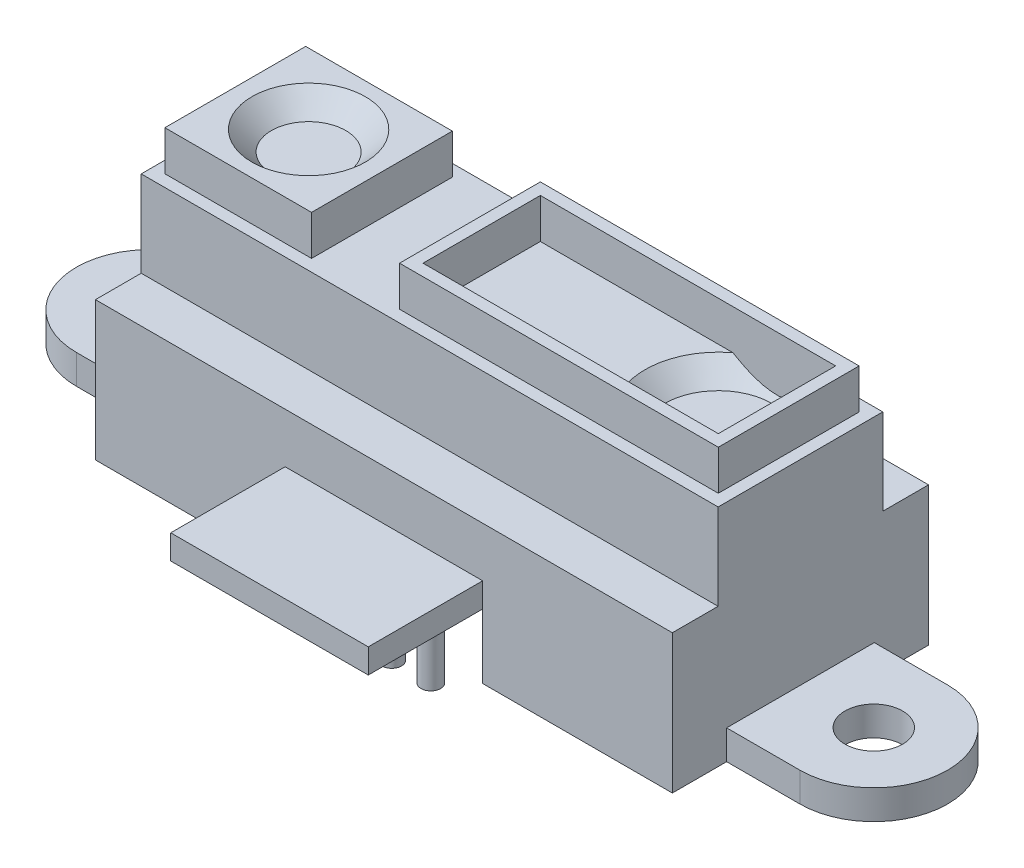
SolidWorks part; units mm, degrees
ref_plane "Front Plane" through (0, 0, 0) normal (0, 0, 1) x (1, 0, 0)
ref_plane "Top Plane" through (0, 0, 0) normal (0, 1, 0) x (1, 0, 0)
ref_plane "Right Plane" through (0, 0, 0) normal (1, 0, 0) x (0, 0, -1)
sketch "Sketch1" plane through (0, 0, 0) normal (0, 1, 0) x (1, 0, 0)
  line L0 (-24.667, 0) -> (35.816, 0) construction
  line L1 (-14.75, 6.55) -> (14.75, 6.55)
  line L2 (-14.75, 6.55) -> (-14.75, -6.55)
  line L3 (-14.75, -6.55) -> (14.75, -6.55)
  line L4 (14.75, 6.55) -> (14.75, -6.55)
  line L5 (-14.75, 6.55) -> (14.75, -6.55) construction
  line L6 (-14.75, -6.55) -> (14.75, 6.55) construction
  line L7 (-22.275, 0) -> (-22.275, -6.55) construction
  line L8 (-22.275, -6.55) -> (-14.75, -6.55) construction
  line L9 (0, 6.55) -> (0, -6.55) construction
  line L10 (-18.5, 3.775) -> (-14.75, 3.775)
  line L11 (-18.5, -3.775) -> (-14.75, -3.775)
  line L12 (18.5, 3.775) -> (14.75, 3.775)
  line L13 (18.5, -3.775) -> (14.75, -3.775)
  circle A0 centre (-18.5, 0) radius 3.775
  circle A1 centre (-18.5, 0) radius 1.4736
  circle A2 centre (18.5, 0) radius 1.4736
  circle A3 centre (18.5, 0) radius 3.775
  point P0 (0, 0)
  dimension "D4" = 7.55
  dimension "D5" = 2.9472
  dimension "D1" = 13.1
  dimension "D2" = 29.5
  dimension "D3" = 44.55
extrude "Boss-Extrude1" add sketch "Sketch1" along normal blind 1.5 contours A0 L2 A1 | A0 L11 L2 | L2 A0 | A0 L2 L10 | L4 A3 L1 L2 A0 L3 | L13 A3 L4 | A3 L4 A2 | L4 A3 L12 | A3 L4 region at (0, 0, 0) region at (-15.5926, 0, -2.9582) region at (15.5926, 0, -2.9582) region at (-14.74, 0, 0) region at (-14.8566, 0, 0) region at (16.0596, 0, -2.7389) region at (14.74, 0, 0) region at (-15.5926, 0, 2.9582) region at (15.5926, 0, 2.9582)
sketch "Sketch2" plane through (0, 1.5, 0) normal (0, 1, 0) x (1, 0, 0)
  line L1 (14.75, 6.55) -> (-14.75, 6.55)
  line L2 (14.75, 6.55) -> (14.75, -6.55)
  line L3 (14.75, -6.55) -> (-14.75, -6.55)
  line L4 (-14.75, 6.55) -> (-14.75, -6.55)
  line L5 (14.75, 6.55) -> (-14.75, -6.55) construction
  line L6 (14.75, -6.55) -> (-14.75, 6.55) construction
  point P0 (0, 0)
extrude "Boss-Extrude2" add sketch "Sketch2" along normal offset from surface (5.6 mm away) 7.1 up to face at (0, 0, 0)
sketch "Sketch3" plane through (0, 7.1, 0) normal (0, 1, 0) x (1, 0, 0)
  line L0 (14.75, -6.55) -> (14.75, 6.55) construction
  line L1 (-14.75, 4.21) -> (14.75, 4.21)
  line L2 (-14.75, 4.21) -> (-14.75, -4.21)
  line L3 (-14.75, -4.21) -> (14.75, -4.21)
  line L4 (14.75, 4.21) -> (14.75, -4.21)
  line L5 (-14.75, 4.21) -> (14.75, -4.21) construction
  line L6 (-14.75, -4.21) -> (14.75, 4.21) construction
  point P0 (0, 0)
  dimension "D1" = 8.42
extrude "Boss-Extrude3" add sketch "Sketch3" along normal offset from surface (4.4 mm away) 11.5 up to face at (0, 0, 0)
sketch "Sketch4" plane through (0, 11.5, 0) normal (0, 1, 0) x (1, 0, 0)
  line L0 (-14.75, 0) -> (14.75, 0) construction
  line L1 (-14.75, 4.21) -> (-14.75, -4.21) construction
  line L2 (14.75, -3.775) -> (14.75, 3.775) construction
  line L3 (-14.15, 3.6) -> (-14.75, 3.6) construction
  line L4 (-14.15, 3.6) -> (-6.65, 3.6)
  line L5 (-14.15, 3.6) -> (-14.15, -3.6)
  line L6 (-14.15, -3.6) -> (-6.65, -3.6)
  line L7 (-6.65, 3.6) -> (-6.65, -3.6)
  line L8 (-14.15, 3.6) -> (-6.65, -3.6) construction
  line L9 (-14.15, -3.6) -> (-6.65, 3.6) construction
  line L10 (-2.15, 3.6) -> (14.15, 3.6)
  line L11 (-2.15, 3.6) -> (-2.15, -3.6)
  line L12 (-2.15, -3.6) -> (14.15, -3.6)
  line L13 (14.15, 3.6) -> (14.15, -3.6)
  line L14 (-2.15, 3.6) -> (14.15, -3.6) construction
  line L15 (-2.15, -3.6) -> (14.15, 3.6) construction
  line L16 (14.15, 3.6) -> (14.75, 3.6) construction
  line L17 (13.55, 3) -> (14.15, 3) construction
  line L18 (-1.55, -3) -> (13.55, -3)
  line L19 (-1.55, -3) -> (-1.55, 3)
  line L20 (-1.55, 3) -> (13.55, 3)
  line L21 (13.55, -3) -> (13.55, 3)
  line L22 (-1.55, -3) -> (13.55, 3) construction
  line L23 (-1.55, 3) -> (13.55, -3) construction
  line L24 (13.55, 3) -> (13.55, 3.6) construction
  point P6 (-10.4, 0)
  point P11 (6, 0)
  point P16 (6, 0)
  dimension "D1" = 7.5
  dimension "D2" = 7.2
  dimension "D3" = 0.6
  dimension "D4" = 16.3
  dimension "D5" = 0.6
extrude "Boss-Extrude4" add sketch "Sketch4" along normal offset from surface (2.04 mm away) 13.54 contours L7 L4 L5 L6 | L13 L10 L11 L12 L21 L18 L19 L20 region at (-10.4, 11.5, 0) region at (6, 11.5, -3.4218) up to face at (0, 0, 0)
sketch "Sketch5" plane through (0, 13.54, 0) normal (0, 1, 0) x (1, 0, 0)
  line L0 (-14.15, 3.6) -> (-6.65, -3.6) construction
  circle A0 centre (-10.4, 0) radius 2.9
  dimension "D1" = 5.8
extrude "Cut-Extrude1" cut sketch "Sketch5" against normal blind 1
sketch "Sketch6" plane through (0, 11.5, 0) normal (0, 1, 0) x (1, 0, 0)
  line L0 (-1.55, 0) -> (13.55, 0) construction
  line L1 (-1.55, -3) -> (-1.55, 3) construction
  line L2 (13.55, -3) -> (13.55, 3) construction
  line L3 (13.55, -3) -> (13.55, 3) construction
  line L8 (13.55, -3) -> (13.55, 3)
  line L9 (13.55, 3) -> (-1.55, 3)
  line L10 (-1.55, 3) -> (-1.55, -3)
  line L11 (-1.55, -3) -> (13.55, -3)
  line L12 (13.55, -3) -> (13.55, 3)
  line L13 (13.55, 3) -> (-1.55, 3)
  line L14 (-1.55, 3) -> (-1.55, -3)
  line L15 (-1.55, -3) -> (13.55, -3)
  circle A0 centre (10.55, 0) radius 3.75
  line M5 (13.55, -3) -> (13.55, 3)
  dimension "D1" = 7.5
  dimension "D2" = 3
  dimension "D3" = 0
extrude "Cut-Extrude2" cut sketch "Sketch6" against normal blind 1 contours A0 L0 L13 M5 | L0 A0 L15 L12 region at (10.3463, 11.5, -1.4258) region at (10.3463, 11.5, 1.4258)
chamfer "Chamfer1" distance 1 angle 45 2 edges at (6.8, 10.5, 0) (-10.4, 12.54, 2.9)
sketch "Sketch7" plane through (0, 0, 6.55) normal (0, 0, 1) x (1, 0, 0)
  line L0 (0, 0) -> (0, 7.1) construction
  line L1 (-14.75, 7.1) -> (14.75, 7.1) construction
  line L2 (-14.75, 0) -> (14.75, 0) construction
  line L3 (-5.05, 4.55) -> (5.05, 4.55)
  line L4 (-5.05, 4.55) -> (-5.05, 3.3)
  line L5 (-5.05, 3.3) -> (5.05, 3.3)
  line L6 (5.05, 4.55) -> (5.05, 3.3)
  line L7 (-5.05, 4.55) -> (5.05, 3.3) construction
  line L8 (-5.05, 3.3) -> (5.05, 4.55) construction
  point P5 (0, 3.925)
  dimension "D1" = 3.3
  dimension "D2" = 1.25
  dimension "D3" = 10.1
extrude "Boss-Extrude5" add sketch "Sketch7" along normal blind 5.85
sketch "Sketch8" plane through (0, 0, 0) normal (0, -1, 0) x (1, 0, 0)
  line L0 (-13.95, 5.75) -> (-14.75, 5.75) construction
  line L1 (13.95, 5.75) -> (-13.95, 5.75)
  line L2 (13.95, 5.75) -> (13.95, -5.75)
  line L3 (13.95, -5.75) -> (-13.95, -5.75)
  line L4 (-13.95, 5.75) -> (-13.95, -5.75)
  line L5 (13.95, 5.75) -> (-13.95, -5.75) construction
  line L6 (13.95, -5.75) -> (-13.95, 5.75) construction
  line L7 (-14.75, 3.775) -> (-14.75, 6.55) construction
  line L8 (-13.95, 5.75) -> (-13.95, 6.55) construction
  line L9 (-14.75, 6.55) -> (14.75, 6.55) construction
  line L10 (5.05, 12.4) -> (5.05, 6.55) construction
  line L11 (-5.05, 12.4) -> (5.05, 12.4)
  line L12 (-5.05, 12.4) -> (-5.05, 5.75)
  line L13 (-5.05, 5.75) -> (5.05, 5.75)
  line L14 (5.05, 12.4) -> (5.05, 5.75)
  point P0 (0, 0)
  line M7 (14.75, 6.55) -> (-14.75, 6.55)
  dimension "D1" = 0.8
extrude "Cut-Extrude3" cut sketch "Sketch8" against normal up to surface (3.3 mm away) contours L1 L4 L3 L2 | L14 L12 L1 M7 region at (0, 0, 0) region at (0, 0, 6.15) up to face at (0, 3.3, 9.475)
sketch "Sketch9" plane through (0, 3.3, 0) normal (0, -1, 0) x (1, 0, 0)
  line L0 (-5.05, 6.15) -> (5.05, 6.15) construction
  line L1 (-5.05, 6.55) -> (-5.05, 5.75) construction
  line L2 (5.05, 6.55) -> (5.05, 5.75) construction
  line L3 (0, 12.4) -> (0, -6.55) construction
  line L4 (-5.05, 12.4) -> (5.05, 12.4) construction
  line L5 (-14.75, -6.55) -> (14.75, -6.55) construction
  circle A0 centre (0, 6.15) radius 0.5
  circle A1 centre (-2, 6.15) radius 0.5
  circle A2 centre (2, 6.15) radius 0.5
  dimension "D1" = 1
  dimension "D2" = 2
extrude "Boss-Extrude6" add sketch "Sketch9" along normal blind 5 separate body
